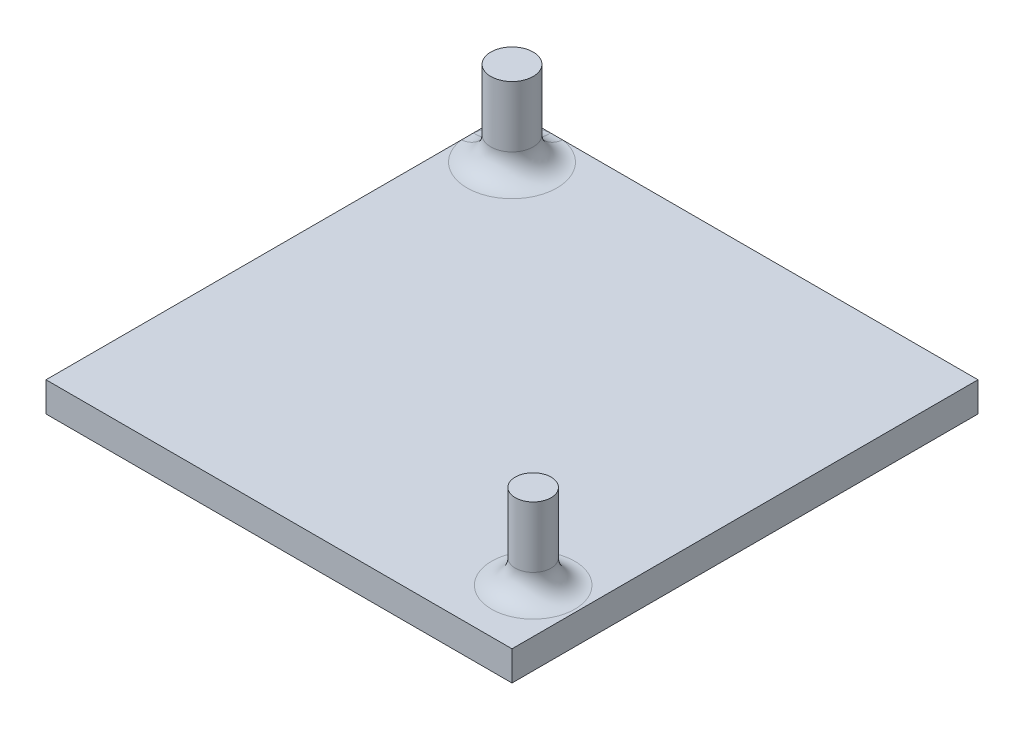
SolidWorks part; units mm, degrees
ref_plane "Front Plane" through (0, 0, 0) normal (0, 0, 1) x (1, 0, 0)
ref_plane "Top Plane" through (0, 0, 0) normal (0, 1, 0) x (1, 0, 0)
ref_plane "Right Plane" through (0, 0, 0) normal (1, 0, 0) x (0, 0, -1)
sketch "Sketch1" plane through (0, 0, 0) normal (0, 1, 0) x (1, 0, 0)
  line L1 (-27.5, 27.5) -> (27.5, 27.5)
  line L2 (-27.5, 27.5) -> (-27.5, -27.5)
  line L3 (-27.5, -27.5) -> (27.5, -27.5)
  line L4 (27.5, 27.5) -> (27.5, -27.5)
  line L5 (-27.5, 27.5) -> (27.5, -27.5) construction
  line L6 (-27.5, -27.5) -> (27.5, 27.5) construction
  circle A0 centre (22.25, -19.75) radius 2.5 construction
  circle A1 centre (-22.25, 22.25) radius 2.5 construction
  point P0 (0, 0)
  dimension "D5" = 5
  dimension "D1" = 55
  dimension "D2" = 5.25
  dimension "D3" = 19.75
  dimension "D4" = 5.25
extrude "Boss-Extrude1" add sketch "Sketch1" along normal blind 3.5
sketch "Sketch2" plane through (0, 3.5, 0) normal (0, 1, 0) x (1, 0, 0)
  line L0 (27.5, 27.5) -> (-27.5, 27.5) construction
  line L1 (-27.5, 27.5) -> (-27.5, -27.5) construction
  line L2 (27.5, -27.5) -> (27.5, 27.5) construction
  circle A0 centre (-22.25, 22.25) radius 2.5
  circle A1 centre (22.25, -19.75) radius 2.1106
  dimension "D5" = 5
  dimension "D1" = 5.25
  dimension "D2" = 5.25
  dimension "D3" = 5.25
  dimension "D4" = 19.75
extrude "Boss-Extrude2" add sketch "Sketch2" along normal blind 10
fillet "Fillet1" radius 2.8 2 edges at (22.25, 3.5, 21.8606) (-22.25, 3.5, -19.75)
sketch "Lightweighting Future" plane through (0, 3.5, 0) normal (0, 1, 0) x (1, 0, 0)
  line L0 (27.5, 27.5) -> (-21.5237, 27.5) construction
  line L1 (-23.5, 23.5) -> (23.5, 23.5)
  line L2 (-23.5, 23.5) -> (-23.5, -23.5)
  line L3 (-23.5, -23.5) -> (23.5, -23.5)
  line L4 (23.5, 23.5) -> (23.5, -23.5)
  line L5 (-23.5, 23.5) -> (23.5, -23.5) construction
  line L6 (-23.5, -23.5) -> (23.5, 23.5) construction
  line L7 (27.5, -27.5) -> (27.5, 27.5) construction
  line L8 (-16.9407, 18.0013) -> (-0.1519, 1.2126)
  arc A0 (-27.5, 21.5237) -> (-21.5237, 27.5) centre (-22.25, 22.25) ccw construction
  arc A1 (-27.5, 21.5237) -> (-21.5237, 27.5) centre (-22.25, 22.25) ccw
  circle A2 centre (22.25, -19.75) radius 4.9106 construction
  circle A3 centre (22.25, -19.75) radius 4.9106
  arc A4 (-28.9858, 21.3182) -> (-21.3182, 28.9858) centre (-22.25, 22.25) ccw
  point P0 (0, 0)
  dimension "D1" = 4
  dimension "D2" = 4
  dimension "D4" = 1.5
  dimension "D3" = 1.5
